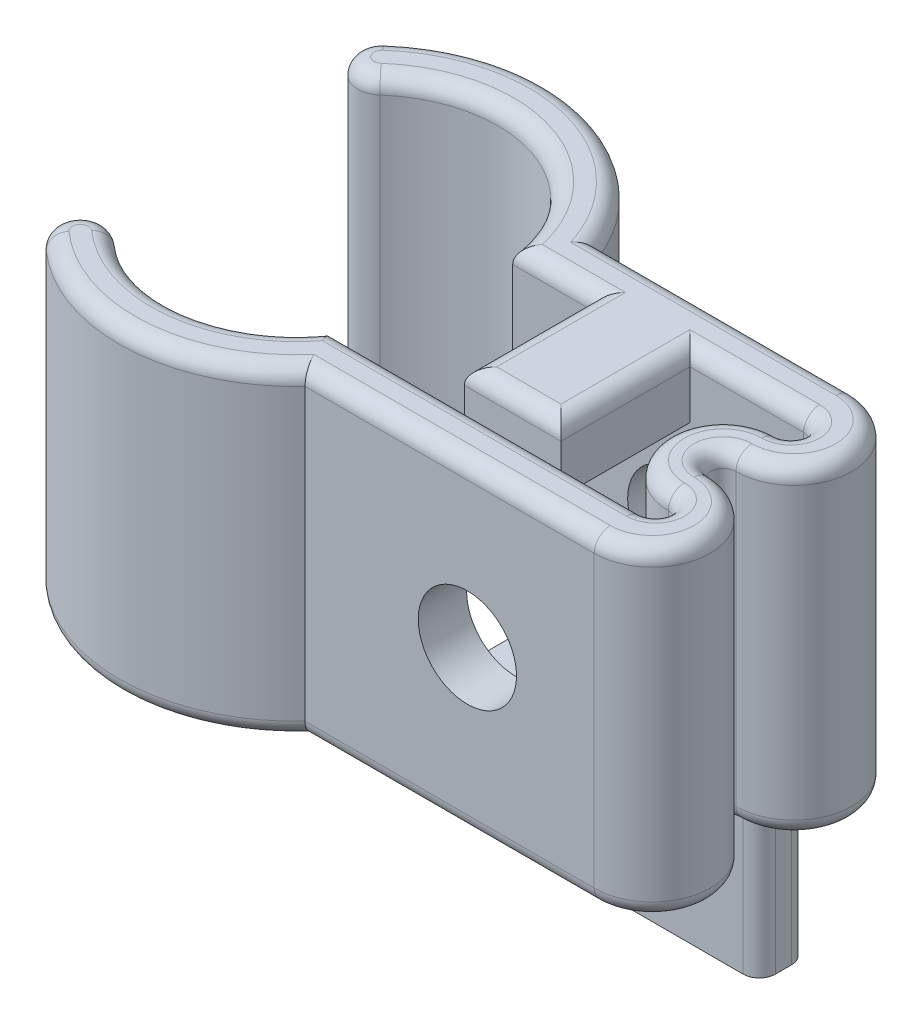
SolidWorks part; units mm, degrees
ref_plane "Front Plane" through (0, 0, 0) normal (0, 0, 1) x (1, 0, 0)
ref_plane "Top Plane" through (0, 0, 0) normal (0, 1, 0) x (1, 0, 0)
ref_plane "Right Plane" through (0, 0, 0) normal (1, 0, 0) x (0, 0, -1)
sketch "Sketch1" plane through (0, 0, 0) normal (0, 1, 0) x (1, 0, 0)
  line L0 (0, 0) -> (26, 0) construction
  line L1 (0, 0) -> (0, 2) construction
  line L2 (0, 0) -> (0, -2.5) construction
  line L3 (26, 0) -> (26, 3) construction
  line L4 (26, 3) -> (3.2949, 3) construction
  line L5 (26, 3) -> (7.9373, 3)
  line L6 (26, 0) -> (26, -7) construction
  line L7 (26, -7) -> (-11.1011, -7) construction
  line L8 (26, -7) -> (6.6144, -7)
  line L9 (10.247, 6) -> (26, 6)
  line L10 (8.0467, -10) -> (26, -10)
  arc A0 (7.9373, 3) -> (-5.3, 7.9925) centre (0, 2) ccw
  arc A1 (6.6144, -7) -> (-5.3, -8.4925) centre (0, -2.5) cw
  arc A2 (-5.3, 7.9925) -> (-7.2875, 10.2397) centre (-6.2937, 9.1161) cw
  arc A3 (-7.2875, 10.2397) -> (10.247, 6) centre (0, 2) cw
  arc A4 (-5.3, -8.4925) -> (-7.2875, -10.7397) centre (-6.2937, -9.6161) ccw
  arc A5 (-7.2875, -10.7397) -> (8.0467, -10) centre (0, -2.5) ccw
  arc A6 (26, 3) -> (26, 1.4) centre (26, 2.2) cw
  arc A7 (26, 1.4) -> (26, -5.4) centre (26, -2) ccw
  arc A8 (26, -5.4) -> (26, -7) centre (26, -6.2) cw
  arc A9 (26, 6) -> (26, -1.2) centre (26, 2.4) cw
  arc A10 (26, -1.2) -> (26, -2.8) centre (26, -2) ccw
  arc A11 (26, -2.8) -> (26, -10) centre (26, -6.4) cw
  dimension "D5" = 8
  dimension "D7" = 8
  dimension "D9" = 1.5
  dimension "D11" = 11
  dimension "D12" = 1.5
  dimension "D14" = 11
  dimension "D15" = 3.6
  dimension "D16" = 0.8
  dimension "D17" = 0.8
  dimension "D18" = 3.6
  dimension "D20" = 0.8
  dimension "D1" = 26
  dimension "D2" = 2
  dimension "D3" = 2.5
  dimension "D4" = 3
  dimension "D6" = 7
  dimension "D8" = 5.3
  dimension "D10" = 3
  dimension "D13" = 3
  dimension "D19" = 10
extrude "Boss-Extrude1" add sketch "Sketch1" along normal blind 20
sketch "Sketch2" plane through (0, 0, -6) normal (0, 0, -1) x (-1, 0, 0)
  line L0 (-18.1235, 20) -> (-18.1235, 0) construction
  line L1 (-26, 20) -> (-10.247, 20) construction
  line L2 (-26, 0) -> (-10.247, 0) construction
  line L4 (-18.1235, 3.5726) -> (-12.5572, 6.7863)
  line L5 (-12.5572, 6.7863) -> (-12.5572, 13.2137)
  line L6 (-12.5572, 13.2137) -> (-18.1235, 16.4274)
  line L7 (-18.1235, 16.4274) -> (-23.6897, 13.2137)
  line L8 (-23.6897, 13.2137) -> (-23.6897, 6.7863)
  line L9 (-23.6897, 6.7863) -> (-18.1235, 3.5726)
  circle A0 centre (-18.1235, 10) radius 6.4274 construction
extrude "Cut-Extrude1" cut sketch "Sketch2" against normal blind 1.5
sketch "Sketch3" plane through (0, 0, -4.5) normal (0, 0, -1) x (-1, 0, 0)
  line L0 (-18.1235, 16.4274) -> (-18.1235, 3.5726) construction
  circle A0 centre (-18.1235, 10) radius 3.05
  dimension "D1" = 6.1
extrude "Cut-Extrude2" cut sketch "Sketch3" against normal through all
sketch "Sketch4" plane through (0, 0, -3) normal (0, 0, 1) x (1, 0, 0)
  line L0 (7.9373, 20) -> (7.9373, 0) construction
  line L1 (8.0467, 20) -> (26, 20) construction
  line L4 (8.0467, 0) -> (26, 0) construction
  line L7 (12.9373, 20) -> (18.9373, 20)
  line L8 (12.9373, 20) -> (12.9373, 16)
  line L9 (12.9373, 16) -> (18.9373, 16)
  line L10 (18.9373, 20) -> (18.9373, 16)
  line L11 (12.9373, 0) -> (18.9373, 0)
  line L12 (12.9373, 0) -> (12.9373, 4)
  line L13 (12.9373, 4) -> (18.9373, 4)
  line L14 (18.9373, 0) -> (18.9373, 4)
  dimension "D1" = 4
  dimension "D2" = 4
  dimension "D3" = 5
  dimension "D4" = 6
extrude "Boss-Extrude2" add sketch "Sketch4" along normal blind 8
fillet "Fillet1" radius 1 20 edges at (-7.4173, 20, -8.1223) (2.5852, 20, -12.6919) (18.1235, 20, -6) (29.6, 20, -2.4) (25.2, 20, 2) (29.6, 20, 6.4) (17.0234, 20, 10) (0.53, 20, 13.4872) (-7.4173, 20, 8.6223) (0.9944, 20, 10.438) (16.3072, 20, 7) (26.8, 20, 6.2) (22.6, 20, 2) (26.8, 20, -2.2) (22.4686, 20, -3) (18.9373, 20, 1) (15.9373, 20, 5) (12.9373, 20, 1) (10.4373, 20, -3) (2.8231, 20, -9.4853)
sketch "Sketch6" plane through (0, 0, 0) normal (0, -1, 0) x (1, 0, 0)
  line L0 (7.9373, -3) -> (12.9373, -3) construction
  line L1 (11.247, -3) -> (23.247, -3)
  line L2 (11.247, -3) -> (11.247, -6)
  line L3 (11.247, -6) -> (23.247, -6)
  line L4 (23.247, -3) -> (23.247, -6)
  line L5 (26, -6) -> (10.247, -6) construction
  dimension "D1" = 1
  dimension "D2" = 12
extrude "Boss-Extrude3" add sketch "Sketch6" along normal blind 12
sketch "Sketch7" plane through (0, 0, -6) normal (0, 0, -1) x (-1, 0, 0)
  line L0 (-11.247, -6) -> (-23.247, -6) construction
  line L1 (-11.247, -12) -> (-11.247, 0) construction
  line L2 (-23.247, -12) -> (-23.247, 0) construction
  circle A0 centre (-17.247, -6) radius 3.95
  dimension "D1" = 7.9
extrude "Cut-Extrude3" cut sketch "Sketch7" against normal blind 1
sketch "Sketch8" plane through (0, 0, -5) normal (0, 0, -1) x (-1, 0, 0)
  circle A0 centre (-17.247, -6) radius 2.05
  dimension "D1" = 4.1
extrude "Cut-Extrude4" cut sketch "Sketch8" against normal through all
fillet "Fillet3" radius 1 8 edges at (-7.4173, 0, -8.1223) (2.5852, 0, -12.6919) (2.8231, 0, -9.4853)
fillet "Fillet4" radius 1 16 edges at (29.6, 0, -2.4) (25.2, 0, 2) (29.6, 0, 6.4) (17.0234, 0, 10) (0.53, 0, 13.4872) (-7.4173, 0, 8.6223) (0.9944, 0, 10.438) (16.3072, 0, 7) (26.8, 0, 6.2) (22.6, 0, 2) (26.8, 0, -2.2)
fillet "Fillet6" radius 1 5 edges at (15.9373, 0, 5)
